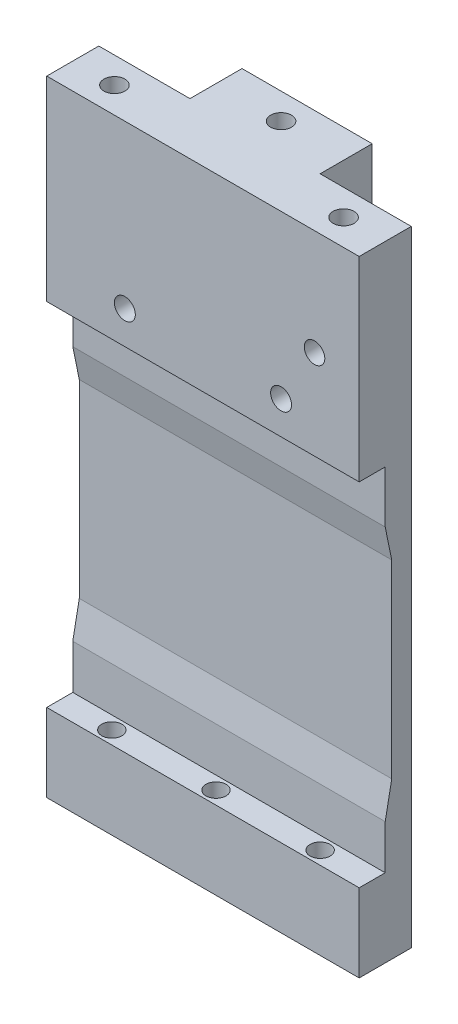
SolidWorks part; units mm, degrees
material "6061 Alloy"
ref_plane "Front Plane" through (0, 0, 0) normal (0, 0, 1) x (1, 0, 0)
ref_plane "Top Plane" through (0, 0, 0) normal (0, 1, 0) x (1, 0, 0)
ref_plane "Right Plane" through (0, 0, 0) normal (1, 0, 0) x (0, 0, -1)
sketch "Sketch1" plane through (0, 0, 0) normal (0, 1, 0) x (1, 0, 0)
  line L0 (-15.875, 6.35) -> (-15.875, 19.05)
  line L1 (38.1, -6.35) -> (-38.1, -6.35)
  line L2 (38.1, -6.35) -> (38.1, 6.35)
  line L3 (38.1, 6.35) -> (15.875, 6.35)
  line L4 (-38.1, -6.35) -> (-38.1, 6.35)
  line L5 (38.1, -6.35) -> (-38.1, 6.35) construction
  line L6 (38.1, 6.35) -> (-38.1, -6.35) construction
  line L7 (-15.875, 19.05) -> (15.875, 19.05)
  line L8 (15.875, 19.05) -> (15.875, 6.35)
  line L9 (-15.875, 6.35) -> (-38.1, 6.35)
  line L10 (0, 19.05) -> (0, 0) construction
  point P0 (0, 0)
  dimension "D1" = 76.2
  dimension "D2" = 12.7
  dimension "D3" = 31.75
  dimension "D4" = 12.7
extrude "Boss-Extrude1" add sketch "Sketch1" along normal mid plane 152.4
ref_plane "Plane1" through (0, 0, 0) normal (0, 1, 0) x (1, 0, 0)
sketch "Sketch5" plane through (0, 0, 0) normal (0, 1, 0) x (1, 0, 0)
  line L0 (-4.7625, 19.05) -> (-4.7625, 12.7)
  line L1 (15.875, 19.05) -> (-15.875, 19.05) construction
  line L2 (4.7625, 12.7) -> (4.7625, 19.05)
  line L3 (0, 0) -> (0, 12.7) construction
  line L4 (-4.7625, 19.05) -> (4.7625, 19.05)
  arc A0 (-4.7625, 12.7) -> (4.7625, 12.7) centre (0, 12.7) ccw
  point P10 (0, 7.9375)
  dimension "D1" = 11.1125
  dimension "D2" = 9.525
extrude "Cut-Extrude3" cut sketch "Sketch5" against normal mid plane 95.25
sketch "Sketch9" plane through (0, 0, 0) normal (1, 0, 0) x (0, 0, -1)
  line L0 (19.05, -52.3875) -> (12.7, -52.3875)
  line L1 (19.05, -52.3875) -> (19.05, -47.625)
  line L2 (19.05, -47.625) -> (7.9375, -47.625) construction
  line L3 (12.7, -52.3875) -> (12.7, -47.625) construction
  line L4 (7.9375, -47.625) -> (19.05, -47.625)
  arc A0 (12.7, -52.3875) -> (7.9375, -47.625) centre (12.7, -47.625) cw
  dimension "D2" = 90
  dimension "D1" = 4.7625
  dimension "D3" = 11.1125
revolve "Cut-Revolve1" cut sketch "Sketch9" angle 360 about L4
mirror "Mirror1" about plane through (0, 0, 0) normal (0, 1, 0) of "Cut-Revolve1"
ref_plane "Parting Plane" through (0, 0, 0) normal (0, 0, 1) x (1, 0, 0)
sketch "Sketch12" plane through (38.1, 0, 0) normal (1, 0, 0) x (0, 0, -1)
  line L0 (-6.35, -57.15) -> (0, -57.15)
  line L1 (-6.35, 76.2) -> (-6.35, -76.2) construction
  line L2 (0, 45.4834) -> (0, -45.4834) construction
  line L3 (0, -57.15) -> (0, -46.3437)
  line L4 (0, -46.3437) -> (1.5875, -38.1)
  line L5 (1.5875, -38.1) -> (1.5875, 8.129)
  line L6 (1.5875, 8.129) -> (0, 15.875)
  line L7 (0, 15.875) -> (0, 28.575)
  line L8 (0, 28.575) -> (-6.35, 28.575)
  line L9 (-6.35, 28.575) -> (-6.35, -57.15)
  line L11 (-6.35, 76.2) -> (6.35, 76.2) construction
  dimension "D1" = 19.05
  dimension "D2" = 47.625
  dimension "D3" = 85.725
  dimension "D4" = 1.5875
  dimension "D5" = 12.7
extrude "Cut-Extrude4" cut sketch "Sketch12" against normal through all
hole_wizard "#10 (0.1935) Diameter Hole1" positions "Sketch15" profile "Sketch16" hole size "#10" standard "ANSI Inch"
sketch "Sketch15" plane through (0, -76.2, 0) normal (0, -1, 0) x (-1, 0, 0)
  line L0 (38.1, 6.35) -> (38.1, -6.35) construction
  line L1 (-38.1, -6.35) -> (-38.1, 6.35) construction
  line L3 (25.4, -3.175) -> (-25.4, -3.175) construction
  line L4 (38.1, -6.35) -> (-38.1, -6.35) construction
  point P0 (25.4, -3.175)
  point P2 (-25.4, -3.175)
  point P16 (0, -3.175)
  dimension "D1" = 12.7
  dimension "D2" = 12.7
  dimension "D3" = 3.175
sketch "Sketch16" plane through (-25.4, -76.2, 3.175) normal (1, 0, 0) x (0, 0, -1)
  line L0 (0, 0) -> (0, 20.5266)
  line L1 (0, 20.5266) -> (2.4574, 19.05)
  line L2 (2.4574, 19.05) -> (2.4574, 0)
  line L5 (2.4574, 0) -> (0, 0)
  line L10 (0, 20.5266) -> (-2.4575, 19.05) construction
  line L11 (0, -6.35) -> (0, 107.95) construction
  dimension "Hole Dia." = 4.9149
  dimension "Hole Depth" = 19.05
  dimension "Drill Angle" = 118
hole_wizard "1/4-20 Tapped Hole1" positions "Sketch17" profile "Sketch18" tap size "1/4-20" standard "ANSI Inch" end condition through all
sketch "Sketch17" plane through (0, 76.2, 0) normal (0, 1, 0) x (1, 0, 0)
  line L0 (15.875, 19.05) -> (-15.875, 19.05) construction
  line L1 (15.875, 6.35) -> (15.875, 19.05) construction
  point P0 (0, 12.7)
  dimension "D1" = 6.35
  dimension "D2" = 15.875
sketch "Sketch18" plane through (0, 76.2, -12.7) normal (1, 0, 0) x (0, 0, 1)
  line L0 (0, 0) -> (0, 152.4)
  line L1 (0, 152.4) -> (2.5527, 152.4)
  line L2 (2.5527, 152.4) -> (2.5527, 0)
  line L5 (2.5527, 0) -> (0, 0)
  line L11 (0, -6.35) -> (0, 107.95) construction
  dimension "Thru Tap Drill Dia." = 5.1054
  dimension "Thru Tap Drill Depth" = 152.4
cosmetic thread "Hole Thread1" parameters "D2"=6.35
sketch "Sketch19" plane through (0, 0, -6.35) normal (0, 0, -1) x (-1, 0, 0)
  circle A0 centre (-27.209, 50.4369) radius 2.5
  dimension "D1" = 5
extrude "Cut-Extrude5" cut sketch "Sketch19" against normal through all
hole_wizard "1/4-20 Tapped Hole2" positions "Sketch20" profile "Sketch21" tap size "1/4-20" standard "ANSI Inch"
sketch "Sketch20" plane through (0, 76.2, 0) normal (0, 1, 0) x (1, 0, 0)
  point P0 (27.94, 0)
  point P3 (-27.94, 0)
sketch "Sketch21" plane through (27.94, 76.2, 0) normal (1, 0, 0) x (0, 0, 1)
  line L0 (0, 0) -> (0, 22.225)
  line L1 (0, 22.225) -> (2.5527, 20.6912)
  line L2 (2.5527, 20.6912) -> (2.5527, 0)
  line L5 (2.5527, 0) -> (0, 0)
  line L10 (0, 22.225) -> (-2.5527, 20.6912) construction
  line L11 (0, -6.35) -> (0, 107.95) construction
  dimension "Tap Drill Dia." = 5.1054
  dimension "Tap Drill Depth" = 22.225
  dimension "Drill Angle" = 118
cosmetic thread "Hole Thread2" parameters "D1"=38.26, "D2"=6.35
cosmetic thread "Hole Thread3" parameters "D1"=38.26, "D2"=6.35
hole_wizard "1/4-20 Tapped Hole3" positions "Sketch22" profile "Sketch23" tap size "1/4-20" standard "ANSI Inch"
sketch "Sketch22" plane through (0, 0, -19.05) normal (0, 0, -1) x (-1, 0, 0)
  line L0 (9.525, 57.15) -> (-9.525, 57.15) construction
  line L2 (0, 57.15) -> (0, 0) construction
  line L4 (-15.875, -76.2) -> (15.875, -76.2) construction
  line L5 (-9.525, 57.15) -> (-9.525, -66.675) construction
  line L7 (-9.525, -66.675) -> (9.525, -66.675) construction
  point P0 (-9.525, -66.675)
  point P2 (9.525, 57.15)
  point P4 (-9.525, 57.15)
  point P26 (9.525, -66.675)
  dimension "D1" = 19.05
  dimension "D2" = 123.825
  dimension "D3" = 9.525
  dimension "D4" = 19.05
sketch "Sketch23" plane through (9.525, -66.675, -19.05) normal (1, 0, 0) x (0, 1, 0)
  line L0 (0, 0) -> (0, 10.5838)
  line L1 (0, 10.5838) -> (2.5527, 9.05)
  line L2 (2.5527, 9.05) -> (2.5527, 0)
  line L5 (2.5527, 0) -> (0, 0)
  line L10 (0, 10.5838) -> (-2.5527, 9.05) construction
  line L11 (0, -6.35) -> (0, 107.95) construction
  dimension "Tap Drill Dia." = 5.1054
  dimension "Tap Drill Depth" = 9.05
  dimension "Drill Angle" = 118
cosmetic thread "Hole Thread4" parameters "D1"=38.26, "D2"=6.35
cosmetic thread "Hole Thread5" parameters "D1"=38.26, "D2"=6.35
cosmetic thread "Hole Thread6" parameters "D1"=38.26, "D2"=6.35
cosmetic thread "Hole Thread9" parameters "D1"=38.26, "D2"=6.35
hole_wizard "1/4-20 Tapped Hole4" positions "Sketch24" profile "Sketch25" tap size "1/4-20" standard "ANSI Inch"
sketch "Sketch24" plane through (0, 0, 6.35) normal (0, 0, 1) x (1, 0, 0)
  point P0 (19.05, 36.6107)
  point P3 (-19.05, 36.6107)
sketch "Sketch25" plane through (19.05, 36.6107, 6.35) normal (1, 0, 0) x (0, -1, 0)
  line L0 (0, 0) -> (0, 8.89)
  line L1 (0, 8.89) -> (2.5527, 7.3562)
  line L2 (2.5527, 7.3562) -> (2.5527, 0)
  line L5 (2.5527, 0) -> (0, 0)
  line L10 (0, 8.89) -> (-2.5527, 7.3562) construction
  line L11 (0, -6.35) -> (0, 107.95) construction
  dimension "Tap Drill Dia." = 5.1054
  dimension "Tap Drill Depth" = 8.89
  dimension "Drill Angle" = 118
cosmetic thread "Hole Thread7" parameters "D1"=12.7, "D2"=6.35
cosmetic thread "Hole Thread8" parameters "D1"=12.7, "D2"=6.35
